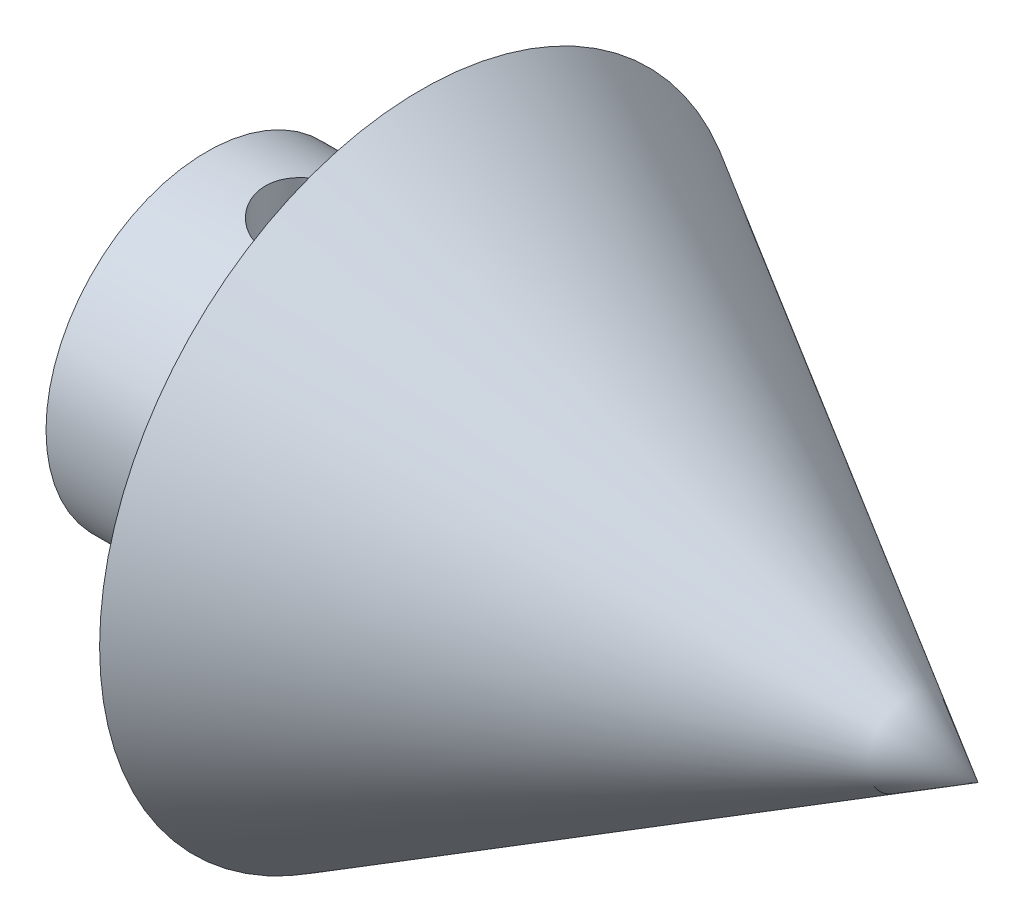
SolidWorks part; units mm, degrees
ref_plane "Alzado" through (0, 0, 0) normal (0, 0, 1) x (1, 0, 0)
ref_plane "Planta" through (0, 0, 0) normal (0, 1, 0) x (1, 0, 0)
ref_plane "Vista lateral" through (0, 0, 0) normal (1, 0, 0) x (0, 0, -1)
sketch "Croquis1" plane through (0, 0, 0) normal (1, 0, 0) x (0, 0, -1)
  line L0 (0, 7.5) -> (0, -7.5) construction
  line L1 (-7.5, 0) -> (7.5, 0) construction
  circle A0 centre (0, 0) radius 7.5
  dimension "D1" = 15
extrude "Saliente-Extruir1" add sketch "Croquis1" along normal blind 10
sketch "Croquis2" plane through (10, 0, 0) normal (1, 0, 0) x (0, 0, -1)
  line L0 (0, 15) -> (0, -15) construction
  circle A0 centre (0, 0) radius 15
  dimension "D1" = 30
extrude "Saliente-Extruir2" add sketch "Croquis2" along normal blind 30 draft 30 separate body
sketch "Croquis5" plane through (0, 0, 0) normal (-1, 0, 0) x (0, 0, 1)
  circle A0 centre (0, 0) radius 4.05
  dimension "D1" = 8.1
extrude "Cortar-Extruir1" cut sketch "Croquis5" against normal blind 15
sketch "Croquis8" plane through (0, 0, 0) normal (-1, 0, 0) x (0, 0, 1)
  line L0 (0, 0) -> (0, 7.5) construction
  circle A0 centre (0, 0) radius 7.5 construction
hole_wizard "Taladro de margen para M41" positions "Croquis3D3" profile "Croquis9" hole size "M4" standard "ISO" end condition up to next
sketch3d "Croquis3D3"
  line L0 (0, 0, 0) -> (10, 0, 0) construction
  line L1 (10, 0, 0) -> (35.9808, 0, 0) construction
  line L2 (10, 0, 0) -> (0, 0, 0) construction
  point P0 (5, 7.5, 0.0155)
  dimension "D1" = 5
sketch "Croquis9" plane through (5, 7.5, 0.0155) normal (1, 0, 0) x (0, -0.0021, 1)
  line L0 (0, 0) -> (0, 7.5)
  line L1 (0, 7.5) -> (2.25, 7.5)
  line L2 (2.25, 7.5) -> (2.25, 0)
  line L5 (2.25, 0) -> (0, 0)
  line L11 (0, -6.35) -> (0, 107.95) construction
  dimension "Diámetro de taladro hasta el siguiente" = 4.5
  dimension "Profundidad de taladro hasta el siguiente" = 7.5
